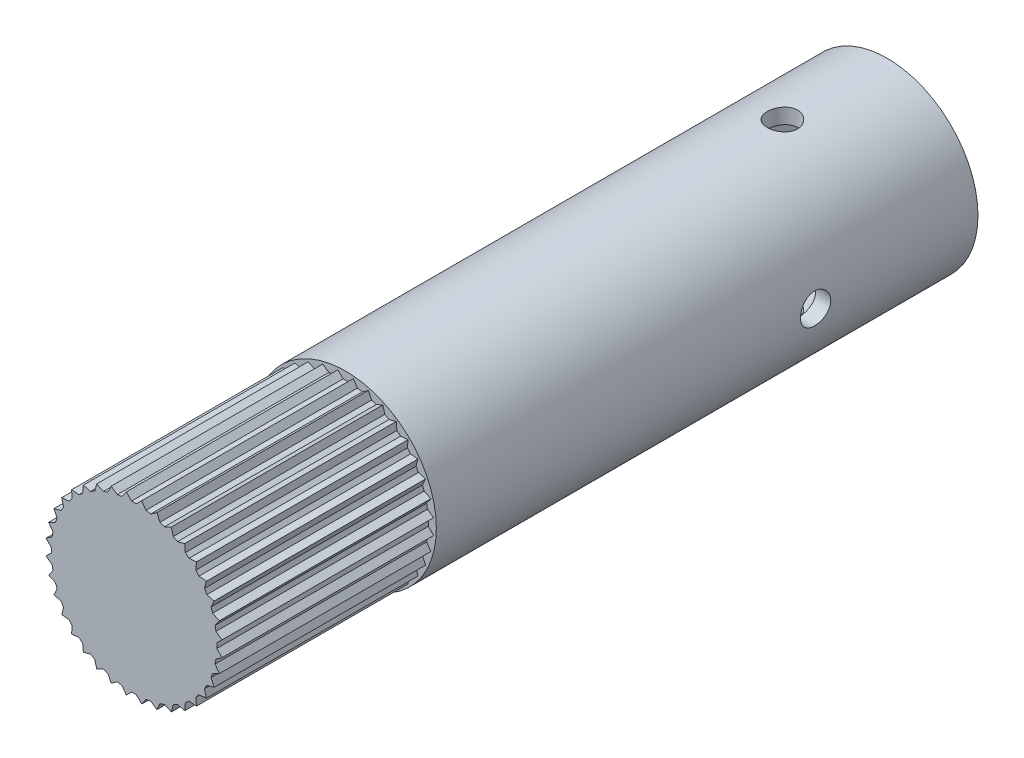
SolidWorks part; units mm, degrees
material "AISI 4130 Steel, annealed at 865C"
ref_plane "X-Y Datum" through (0, 0, 0) normal (0, 0, 1) x (1, 0, 0)
ref_plane "X-Z Datum" through (0, 0, 0) normal (0, 1, 0) x (1, 0, 0)
ref_plane "Y-Z Datum" through (0, 0, 0) normal (1, 0, 0) x (0, 0, -1)
sketch "Sketch9" plane through (0, 0, 0) normal (0, 1, 0) x (1, 0, 0)
  line L0 (16.002, 0) -> (0, 0)
  line L1 (0, 0) -> (0, -382.27)
  line L2 (0, -382.27) -> (-72.2493, -518.1512)
  dimension "D1" = 153.895
  dimension "D2" = 28
  dimension "D3" = 382.27
  dimension "D5" = 16.002
sketch "Sketch5" plane through (0, 0, 0) normal (0, 1, 0) x (1, 0, 0)
  line L0 (7.9375, -101.1961) -> (7.9375, -22.1615)
  line L1 (7.9375, -22.1615) -> (9.525, -22.1615)
  line L2 (9.525, -22.1615) -> (9.525, -101.1961)
  line L3 (9.525, -101.1961) -> (7.9375, -101.1961)
  line L5 (16.002, 0) -> (0, 0) construction
  line L6 (0, 0) -> (0, -382.27) construction
  line L7 (0, -382.27) -> (9.525, -382.27) construction
  line L8 (12.5602, -77.27) -> (0, -77.27) construction
  dimension "D1" = 1.5875
  dimension "D2" = 22.1615
  dimension "D3" = 7.9375
  dimension "D4" = 305
  dimension "D5" = 281.0739
revolve "Revolve2" add sketch "Sketch5" angle 360 about L1
sketch "Sketch6" plane through (0, 0, 0) normal (0, 1, 0) x (1, 0, 0)
  circle A0 centre (0, -33.1635) radius 1.5875 construction
  circle A1 centre (0, -33.1635) radius 1.5875
sketch "Sketch7" plane through (0, 0, 0) normal (1, 0, 0) x (0, 0, -1)
  circle A2 centre (-39.196, 0) radius 1.5875
  circle A4 centre (-39.196, 0) radius 1.5875 construction
extrude "Cut-Extrude5" cut sketch "Sketch7" against normal through all both and the other way through all
extrude "Cut-Extrude6" cut sketch "Sketch6" against normal through all both and the other way through all
sketch "Sketch8" plane through (0, 0, 0) normal (0, 0, 1) x (1, 0, 0)
  line L0 (9.2357, -0.808) -> (8.6817, -0.254)
  line L1 (8.6817, -0.254) -> (8.6817, 0.254)
  line L2 (8.6817, 0.254) -> (9.2357, 0.808)
  line L3 (8.6817, 0) -> (0, 0) construction
  line L4 (8.9551, -2.3995) -> (8.5057, -1.7577)
  line L5 (8.5057, -1.7577) -> (8.5939, -1.2574)
  line L6 (8.5939, -1.2574) -> (9.2357, -0.808)
  line L7 (8.4024, -3.9181) -> (8.0713, -3.208)
  line L8 (8.0713, -3.208) -> (8.245, -2.7306)
  line L9 (8.245, -2.7306) -> (8.9551, -2.3995)
  line L10 (7.5944, -5.3176) -> (7.3916, -4.5608)
  line L11 (7.3916, -4.5608) -> (7.6456, -4.1209)
  line L12 (7.6456, -4.1209) -> (8.4024, -3.9181)
  line L13 (6.5556, -6.5556) -> (6.4873, -5.7751)
  line L14 (6.4873, -5.7751) -> (6.8138, -5.3859)
  line L15 (6.8138, -5.3859) -> (7.5944, -5.3176)
  line L16 (5.3176, -7.5944) -> (5.3859, -6.8138)
  line L17 (5.3859, -6.8138) -> (5.7751, -6.4873)
  line L18 (5.7751, -6.4873) -> (6.5556, -6.5556)
  line L19 (3.9181, -8.4024) -> (4.1209, -7.6456)
  line L20 (4.1209, -7.6456) -> (4.5608, -7.3916)
  line L21 (4.5608, -7.3916) -> (5.3176, -7.5944)
  line L22 (2.3995, -8.9551) -> (2.7306, -8.245)
  line L23 (2.7306, -8.245) -> (3.208, -8.0713)
  line L24 (3.208, -8.0713) -> (3.9181, -8.4024)
  line L25 (0.808, -9.2357) -> (1.2574, -8.5939)
  line L26 (1.2574, -8.5939) -> (1.7577, -8.5057)
  line L27 (1.7577, -8.5057) -> (2.3995, -8.9551)
  line L28 (-0.808, -9.2357) -> (-0.254, -8.6817)
  line L29 (-0.254, -8.6817) -> (0.254, -8.6817)
  line L30 (0.254, -8.6817) -> (0.808, -9.2357)
  line L31 (-2.3995, -8.9551) -> (-1.7577, -8.5057)
  line L32 (-1.7577, -8.5057) -> (-1.2574, -8.5939)
  line L33 (-1.2574, -8.5939) -> (-0.808, -9.2357)
  line L34 (-3.9181, -8.4024) -> (-3.208, -8.0713)
  line L35 (-3.208, -8.0713) -> (-2.7306, -8.245)
  line L36 (-2.7306, -8.245) -> (-2.3995, -8.9551)
  line L37 (-5.3176, -7.5944) -> (-4.5608, -7.3916)
  line L38 (-4.5608, -7.3916) -> (-4.1209, -7.6456)
  line L39 (-4.1209, -7.6456) -> (-3.9181, -8.4024)
  line L40 (-6.5556, -6.5556) -> (-5.7751, -6.4873)
  line L41 (-5.7751, -6.4873) -> (-5.3859, -6.8138)
  line L42 (-5.3859, -6.8138) -> (-5.3176, -7.5944)
  line L43 (-7.5944, -5.3176) -> (-6.8138, -5.3859)
  line L44 (-6.8138, -5.3859) -> (-6.4873, -5.7751)
  line L45 (-6.4873, -5.7751) -> (-6.5556, -6.5556)
  line L46 (-8.4024, -3.9181) -> (-7.6456, -4.1209)
  line L47 (-7.6456, -4.1209) -> (-7.3916, -4.5608)
  line L48 (-7.3916, -4.5608) -> (-7.5944, -5.3176)
  line L49 (-8.9551, -2.3995) -> (-8.245, -2.7306)
  line L50 (-8.245, -2.7306) -> (-8.0713, -3.208)
  line L51 (-8.0713, -3.208) -> (-8.4024, -3.9181)
  line L52 (-9.2357, -0.808) -> (-8.5939, -1.2574)
  line L53 (-8.5939, -1.2574) -> (-8.5057, -1.7577)
  line L54 (-8.5057, -1.7577) -> (-8.9551, -2.3995)
  line L55 (-9.2357, 0.808) -> (-8.6817, 0.254)
  line L56 (-8.6817, 0.254) -> (-8.6817, -0.254)
  line L57 (-8.6817, -0.254) -> (-9.2357, -0.808)
  line L58 (-8.9551, 2.3995) -> (-8.5057, 1.7577)
  line L59 (-8.5057, 1.7577) -> (-8.5939, 1.2574)
  line L60 (-8.5939, 1.2574) -> (-9.2357, 0.808)
  line L61 (-8.4024, 3.9181) -> (-8.0713, 3.208)
  line L62 (-8.0713, 3.208) -> (-8.245, 2.7306)
  line L63 (-8.245, 2.7306) -> (-8.9551, 2.3995)
  line L64 (-7.5944, 5.3176) -> (-7.3916, 4.5608)
  line L65 (-7.3916, 4.5608) -> (-7.6456, 4.1209)
  line L66 (-7.6456, 4.1209) -> (-8.4024, 3.9181)
  line L67 (-6.5556, 6.5556) -> (-6.4873, 5.7751)
  line L68 (-6.4873, 5.7751) -> (-6.8138, 5.3859)
  line L69 (-6.8138, 5.3859) -> (-7.5944, 5.3176)
  line L70 (-5.3176, 7.5944) -> (-5.3859, 6.8138)
  line L71 (-5.3859, 6.8138) -> (-5.7751, 6.4873)
  line L72 (-5.7751, 6.4873) -> (-6.5556, 6.5556)
  line L73 (-3.9181, 8.4024) -> (-4.1209, 7.6456)
  line L74 (-4.1209, 7.6456) -> (-4.5608, 7.3916)
  line L75 (-4.5608, 7.3916) -> (-5.3176, 7.5944)
  line L76 (-2.3995, 8.9551) -> (-2.7306, 8.245)
  line L77 (-2.7306, 8.245) -> (-3.208, 8.0713)
  line L78 (-3.208, 8.0713) -> (-3.9181, 8.4024)
  line L79 (-0.808, 9.2357) -> (-1.2574, 8.5939)
  line L80 (-1.2574, 8.5939) -> (-1.7577, 8.5057)
  line L81 (-1.7577, 8.5057) -> (-2.3995, 8.9551)
  line L82 (0.808, 9.2357) -> (0.254, 8.6817)
  line L83 (0.254, 8.6817) -> (-0.254, 8.6817)
  line L84 (-0.254, 8.6817) -> (-0.808, 9.2357)
  line L85 (2.3995, 8.9551) -> (1.7577, 8.5057)
  line L86 (1.7577, 8.5057) -> (1.2574, 8.5939)
  line L87 (1.2574, 8.5939) -> (0.808, 9.2357)
  line L88 (3.9181, 8.4024) -> (3.208, 8.0713)
  line L89 (3.208, 8.0713) -> (2.7306, 8.245)
  line L90 (2.7306, 8.245) -> (2.3995, 8.9551)
  line L91 (5.3176, 7.5944) -> (4.5608, 7.3916)
  line L92 (4.5608, 7.3916) -> (4.1209, 7.6456)
  line L93 (4.1209, 7.6456) -> (3.9181, 8.4024)
  line L94 (6.5556, 6.5556) -> (5.7751, 6.4873)
  line L95 (5.7751, 6.4873) -> (5.3859, 6.8138)
  line L96 (5.3859, 6.8138) -> (5.3176, 7.5944)
  line L97 (7.5944, 5.3176) -> (6.8138, 5.3859)
  line L98 (6.8138, 5.3859) -> (6.4873, 5.7751)
  line L99 (6.4873, 5.7751) -> (6.5556, 6.5556)
  line L100 (8.4024, 3.9181) -> (7.6456, 4.1209)
  line L101 (7.6456, 4.1209) -> (7.3916, 4.5608)
  line L102 (7.3916, 4.5608) -> (7.5944, 5.3176)
  line L103 (8.9551, 2.3995) -> (8.245, 2.7306)
  line L104 (8.245, 2.7306) -> (8.0713, 3.208)
  line L105 (8.0713, 3.208) -> (8.4024, 3.9181)
  line L106 (9.2357, 0.808) -> (8.5939, 1.2574)
  line L107 (8.5939, 1.2574) -> (8.5057, 1.7577)
  line L108 (8.5057, 1.7577) -> (8.9551, 2.3995)
  circle A0 centre (0, 0) radius 12.7
  circle A1 centre (0, 0) radius 9.271 construction
  circle A2 centre (0, 0) radius 8.6854 construction
  point P153 (0, 0)
  dimension "D1" = 25.4
  dimension "D4" = 18.542
  dimension "D6" = 17.3708
  dimension "D2" = 0.508
  dimension "D3" = 135
  dimension "D5" = 36
ref_plane "Plane1" through (0, 0, 47.5615) normal (0, 0, -1) x (-1, 0, 0)
sketch "Sketch10" plane through (0, 0, 47.5615) normal (0, 0, -1) x (-1, 0, 0)
  circle A0 centre (0, 0) radius 7.9375
  dimension "D1" = 15.875
extrude "Boss-Extrude1" add sketch "Sketch10" against normal up to surface (53.6346 mm away) up to face at (-9.525, 0, 101.1961)
sketch "Sketch11" plane through (0, 0, 22.1615) normal (0, 0, -1) x (-1, 0, 0)
  line L0 (0, 9.525) -> (13.3548, 9.525) construction
  line L1 (0, 9.525) -> (0, 15.4312) construction
  line L2 (-9.525, 0) -> (-9.525, 9.1744) construction
  line L3 (-9.525, 0) -> (-16.674, 0) construction
  circle A0 centre (0, 0) radius 9.525 construction
  point P0 (0, 9.525)
  point P1 (-9.525, 0)
extrude "Cut-Extrude7" cut sketch "Sketch8" along normal blind 25.4 from offset 78.9991
